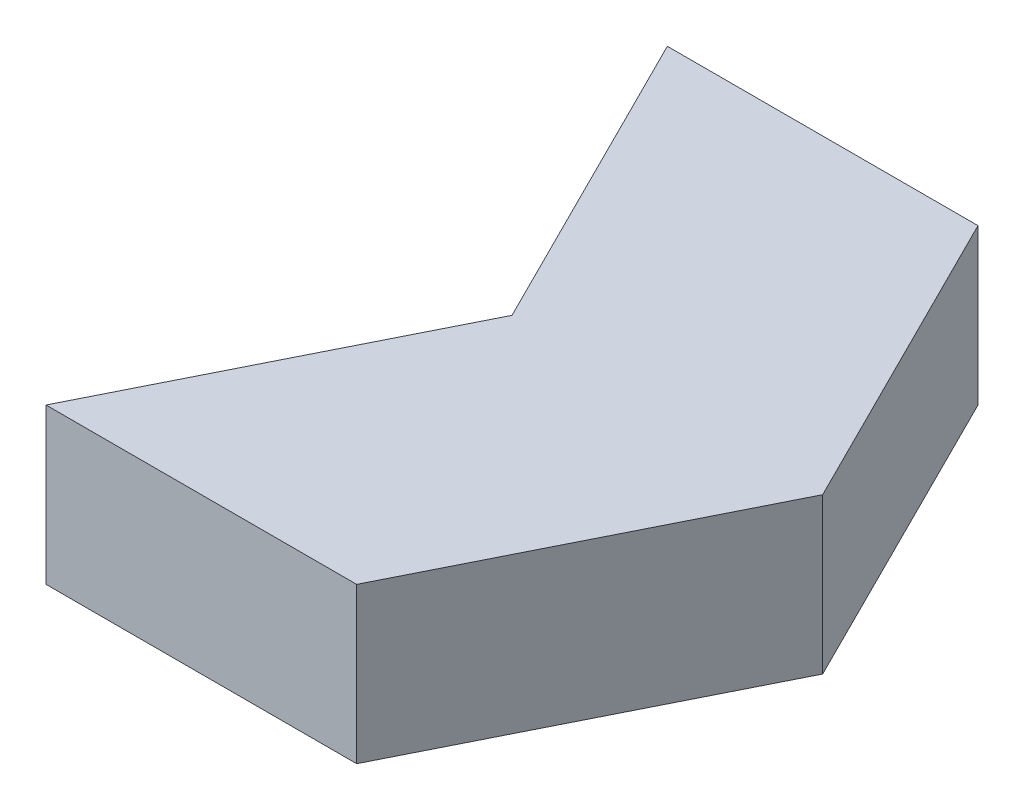
SolidWorks part; units mm, degrees
ref_plane "Front Plane" through (0, 0, 0) normal (0, 0, 1) x (1, 0, 0)
ref_plane "Top Plane" through (0, 0, 0) normal (0, 1, 0) x (1, 0, 0)
ref_plane "Right Plane" through (0, 0, 0) normal (1, 0, 0) x (0, 0, -1)
sketch "Sketch1" plane through (0, 0, 0) normal (0, 1, 0) x (1, 0, 0)
  line L0 (0, 0) -> (12.7, 0)
  line L1 (12.7, 0) -> (19.05, 12.7)
  line L2 (19.05, 12.7) -> (12.7, 25.4)
  line L3 (12.7, 25.4) -> (0, 25.4)
  line L4 (0, 25.4) -> (6.35, 12.7)
  line L5 (6.35, 12.7) -> (0, 0)
  point P5 (0, 0)
  point P8 (0, 0)
  point P9 (0, 0)
  point P10 (0, 0)
  point P11 (0, 0)
  dimension "D1" = 12.7
  dimension "D2" = 25.4
  dimension "D3" = 6.35
  dimension "D5" = 12.7
extrude "Boss-Extrude1" add sketch "Sketch1" along normal blind 6.35
sketch "Sketch2" plane through (0, 0, 0) normal (0, -1, 0) x (1, 0, 0)
  line L0 (19.05, -12.7) -> (6.35, -12.7) construction
  line L1 (6.35, -12.7) -> (0, 0) construction
  circle A0 centre (12.192, -12.7) radius 5.127
  point P7 (0, 0)
  point P8 (0, 0)
  point P9 (0, 0)
  point P10 (0, 0)
  dimension "D1" = 10.254
  dimension "D2" = 5.842
extrude "Cut-Extrude1" cut sketch "Sketch2" against normal blind 2.7 contours A0
sketch "Sketch3" plane through (0, 0, 0) normal (0, -1, 0) x (1, 0, 0)
  line L8 (11.1065, -17.7108) -> (8.8347, -16.5749)
  line L9 (11.1065, -17.7108) -> (9.4026, -21.1185)
  line L10 (8.8347, -16.5749) -> (7.1308, -19.9826)
  line L11 (9.4026, -21.1185) -> (7.1308, -19.9826)
  line L12 (19.05, -12.7) -> (12.7, -25.4) construction
  circle A3 centre (12.192, -12.7) radius 5.127 construction
  dimension "D1" = 2.54
  dimension "D2" = 3.81
extrude "Cut-Extrude2" cut sketch "Sketch3" against normal blind 2.7
equation "\"Arrow Height\"= 1in"
equation "\"Button Height\"= 2in"
equation "\"Button Width\"= 4in"
equation "\"Haptic Diameter\"= 10mm"
equation "\"Haptic Thickness\"= 2.7mm"
equation "\"D2@Sketch1\"=\"Arrow Height\""
equation "\"D5@Sketch1\"=\"Arrow Height\"/2"
equation "\"D1@Sketch2\"=\"Haptic Diameter\" + .01in"
equation "\"D1@Cut-Extrude1\"=\"Haptic Thickness\""
equation "\"D1@Cut-Extrude2\"=\"Haptic Thickness\""
